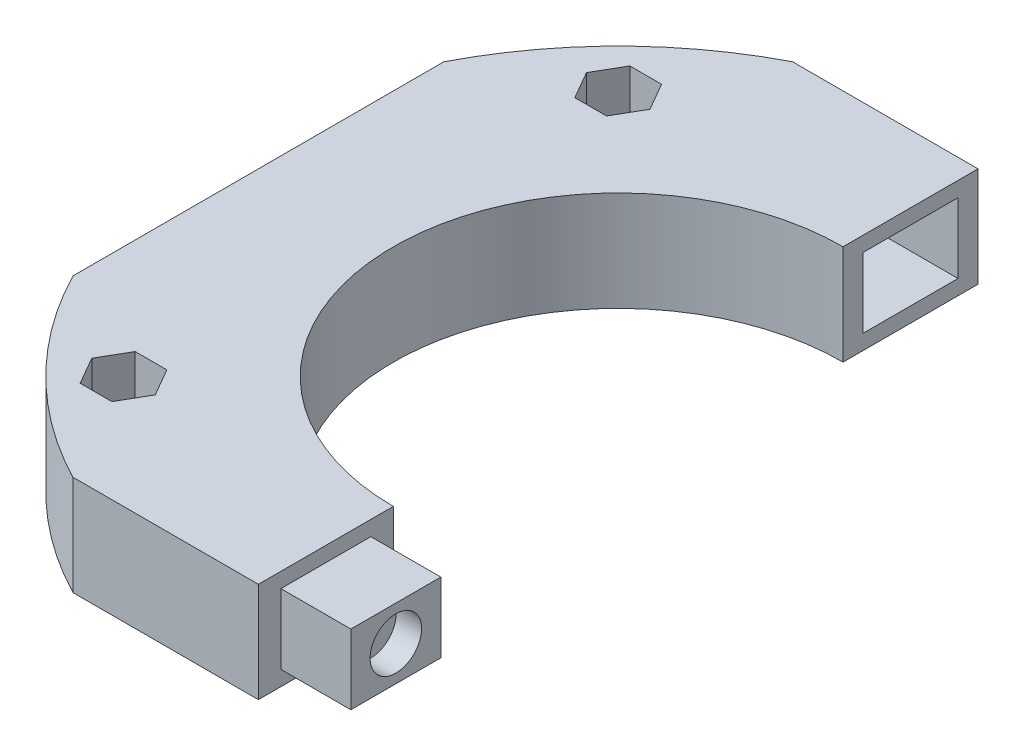
SolidWorks part; units mm, degrees
ref_plane "Front Plane" through (0, 0, 0) normal (0, 0, 1) x (1, 0, 0)
ref_plane "Top Plane" through (0, 0, 0) normal (0, 1, 0) x (1, 0, 0)
ref_plane "Right Plane" through (0, 0, 0) normal (1, 0, 0) x (0, 0, -1)
sketch "Sketch1" plane through (0, 0, 0) normal (0, 1, 0) x (1, 0, 0)
  line L0 (0, 74.1448) -> (0, -72.8187)
  line L1 (-36, -36) -> (36, -36)
  line L2 (-36, -36) -> (-36, 36)
  line L3 (-36, 36) -> (36, 36)
  line L4 (36, -36) -> (36, 36)
  line L5 (-36, -36) -> (36, 36) construction
  line L6 (-36, 36) -> (36, -36) construction
  circle A0 centre (0, 0) radius 22.5
  circle A1 centre (-24.7487, 24.7487) radius 1.5
  circle A2 centre (24.7487, 24.7487) radius 1.5
  circle A3 centre (24.7487, -24.7487) radius 1.5
  circle A4 centre (-24.7487, -24.7487) radius 1.5
  circle A5 centre (0, 0) radius 40.5
  point P0 (0, 0)
  point P21 (0, 0)
  dimension "D1" = 45
  dimension "D5" = 3
  dimension "D2" = 36
  dimension "D3" = 36
  dimension "D4" = 0
  dimension "D7" = 35
  dimension "D8" = 0
  dimension "D9" = 18
  dimension "D6" = 4
extrude "Boss-Extrude1" add sketch "Sketch1" along normal blind 5 and the other way blind 5 contours A0 L0 L3 L2 L1 region at (-0.805, 0, -29.25)
sketch "Sketch2" plane through (0, 5, 0) normal (0, 1, 0) x (1, 0, 0)
  line L0 (-18.554, 36) -> (0, 36) construction
  line L1 (-23.161, 27.4987) -> (-26.3365, 27.4987)
  line L2 (-26.3365, 27.4987) -> (-27.9242, 24.7487)
  line L3 (-27.9242, 24.7487) -> (-26.3365, 21.9987)
  line L4 (-26.3365, 21.9987) -> (-23.161, 21.9987)
  line L5 (-23.161, 21.9987) -> (-21.5733, 24.7487)
  line L6 (-21.5733, 24.7487) -> (-23.161, 27.4987)
  circle A0 centre (-24.7487, 24.7487) radius 2.75 construction
  dimension "D1" = 5.5
  dimension "D2" = 0
extrude "Cut-Extrude1" cut sketch "Sketch2" against normal blind 5
mirror "Mirror1" about plane through (0, 0, 0) normal (0, 0, 1) of "Cut-Extrude1"
sketch "Sketch3" plane through (0, 0, 0) normal (0, 1, 0) x (1, 0, 0)
  line L0 (0, -22.5) -> (0, -36) construction
  line L1 (0, -24.75) -> (7, -24.75)
  line L2 (0, -24.75) -> (0, -33.75)
  line L3 (0, -33.75) -> (7, -33.75)
  line L4 (7, -24.75) -> (7, -33.75)
  line L5 (-18.554, -36) -> (0, -36) construction
  dimension "D1" = 9
  dimension "D2" = 2.25
  dimension "D3" = 7
extrude "Boss-Extrude2" add sketch "Sketch3" against normal blind 3.5 and the other way blind 3.5
sketch "Sketch4" plane through (0, 0, 0) normal (0, -1, 0) x (1, 0, 0)
  line L0 (0, -36) -> (0, -22.5) construction
  line L1 (0, -24.5) -> (-9.4543, -24.5)
  line L2 (0, -24.5) -> (0, -34)
  line L3 (0, -34) -> (-9.4543, -34)
  line L4 (-9.4543, -24.5) -> (-9.4543, -34)
  line L5 (-18.554, -36) -> (0, -36) construction
  dimension "D1" = 9.5
  dimension "D2" = 2
extrude "Cut-Extrude2" cut sketch "Sketch4" against normal blind 3.5 and the other way blind 3.5
sketch "Sketch5" plane through (7, 0, 0) normal (1, 0, 0) x (0, 0, -1)
  line L1 (-33.75, 3.5) -> (-33.75, -3.5) construction
  circle A0 centre (-29.25, 0) radius 2.575
  dimension "D1" = 5.15
  dimension "D2" = 4.5
extrude "Cut-Extrude3" cut sketch "Sketch5" against normal blind 2.55
sketch "Sketch6" plane through (-9.4543, 0, 0) normal (1, 0, 0) x (0, 0, -1)
  circle A0 centre (29.25, 0) radius 2.575
  dimension "D1" = 5.15
  dimension "D2" = 29.25
extrude "Cut-Extrude4" cut sketch "Sketch6" against normal blind 2.55
